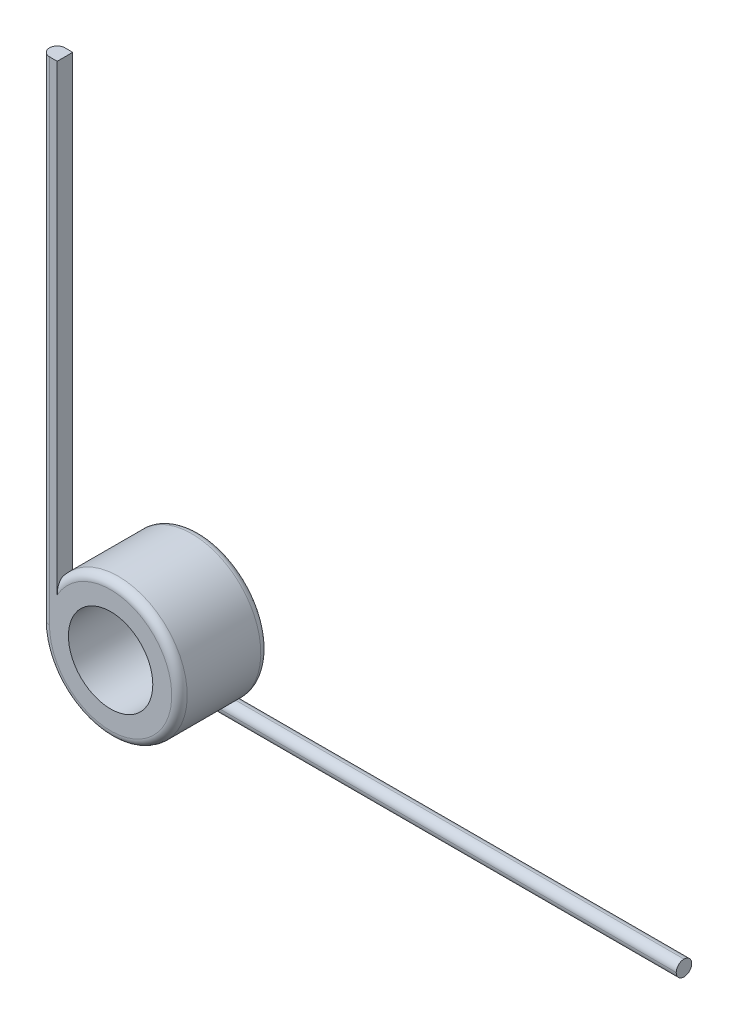
SolidWorks part; units mm, degrees
ref_plane "Front Plane" through (0, 0, 0) normal (0, 0, 1) x (1, 0, 0)
ref_plane "Top Plane" through (0, 0, 0) normal (0, 1, 0) x (1, 0, 0)
ref_plane "Right Plane" through (0, 0, 0) normal (1, 0, 0) x (0, 0, -1)
sketch "Sketch1" plane through (0, 0, 0) normal (0, 0, 1) x (1, 0, 0)
  circle A0 centre (0, 0) radius 7.112
  circle A1 centre (0, 0) radius 4.3561
  dimension "D1" = 14.224
  dimension "D2" = 8.7122
extrude "Boss-Extrude1" add sketch "Sketch1" along normal blind 9.1948
sketch "Sketch2" plane through (0, 0, 9.1948) normal (0, 0, 1) x (1, 0, 0)
  line L0 (-7.112, 0) -> (-7.112, 50.8)
  line L1 (-7.112, 50.8) -> (-5.5118, 50.8)
  line L2 (-5.5118, 50.8) -> (-5.5118, 4.4945)
  line L3 (0, 0) -> (0, -14.6657) construction
  circle A0 centre (0, 0) radius 7.112 construction
  arc A1 (-5.5118, 4.4945) -> (-7.112, 0) centre (0, 0) ccw
  dimension "D1" = 50.8
  dimension "D2" = 1.6002
  dimension "D3" = 180
extrude "Boss-Extrude2" add sketch "Sketch2" against normal blind 1.6002
fillet "Fillet1" radius 0.8001 3 edges at (6.7, -2.3854, 9.1948) (-7.112, 25.4, 7.5946) (-7.112, 25.4, 9.1948)
sketch "Sketch4" plane through (0, 0, 0) normal (0, 0, -1) x (-1, 0, 0)
  line L0 (0, -7.112) -> (-50.8, -7.112)
  line L1 (-50.8, -7.112) -> (-50.8, -5.5118)
  line L2 (-50.8, -5.5118) -> (-4.4945, -5.5118)
  circle A0 centre (0, 0) radius 7.112 construction
  arc A1 (-4.4945, -5.5118) -> (0, -7.112) centre (0, 0) ccw
  dimension "D1" = 1.6002
  dimension "D2" = 50.8
extrude "Boss-Extrude4" add sketch "Sketch4" against normal blind 1.6002
fillet "Fillet2" radius 0.8001 5 edges at (-2.3854, 6.7, 0) (25.4, -7.112, 1.6002) (27.6473, -5.5118, 1.6002) (25.4, -7.112, 0) (27.6473, -5.5118, 0)
equation "\"diam\"= .063"
equation "\"shaft\" = .343"
equation "\"od\" = .56"
equation "\"length\" = .362"
equation "\"D1@Sketch1\"=\"od\""
equation "\"D2@Sketch1\"=\"shaft\""
equation "\"coils\"= 8"
equation "\"D1@Boss-Extrude1\"=\"length\""
equation "\"D1@Boss-Extrude2\"=\"diam\""
equation "\"D2@Sketch2\"=\"diam\""
equation "\"arm\"= 2"
equation "\"D1@Sketch2\"=\"arm\""
equation "\"D2@Sketch4\"=\"arm\""
equation "\"D1@Sketch4\"=\"diam\""
equation "\"D1@Boss-Extrude4\"=\"diam\""
equation "\"D1@Fillet2\"=\"diam\"/2"
equation "\"D1@Fillet1\"=\"diam\"/2"
